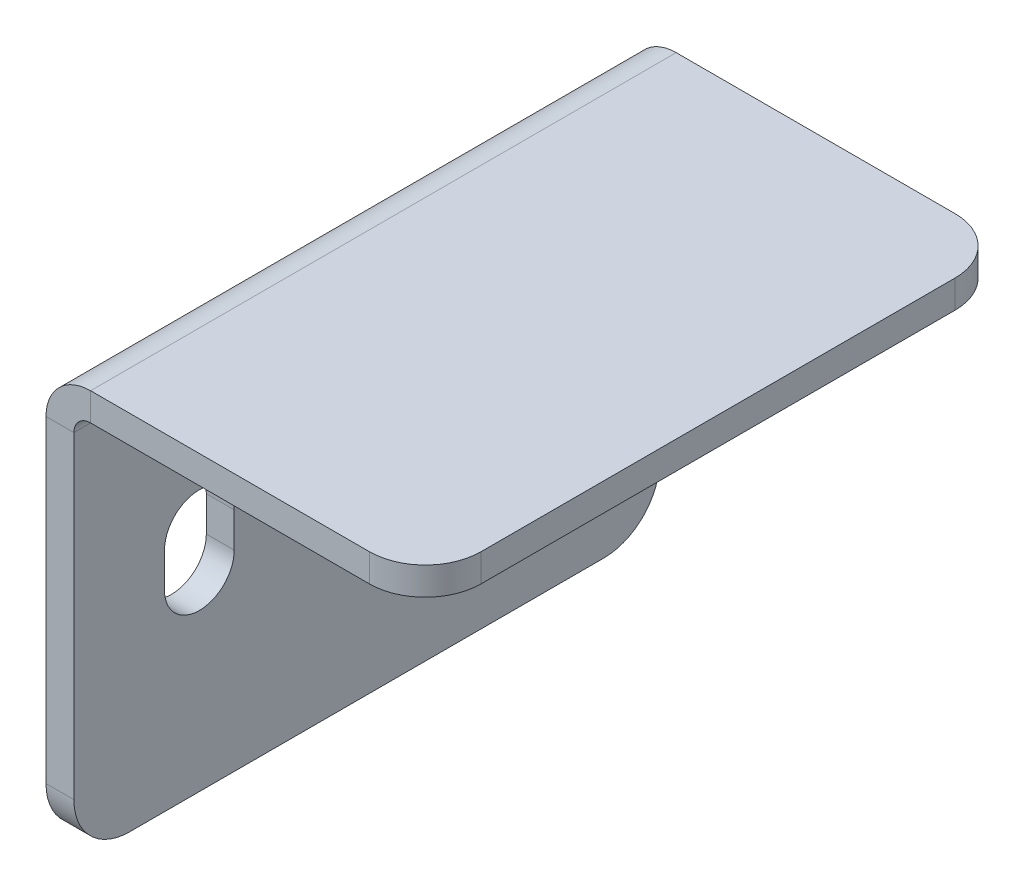
SolidWorks part; units mm, degrees
note: The reader was unsure of these and kept them because the rebuilt part matched: flange length of "Edge-Flange1".
ref_plane "Front Plane" through (0, 0, 0) normal (0, 0, 1) x (1, 0, 0)
ref_plane "Top Plane" through (0, 0, 0) normal (0, 1, 0) x (1, 0, 0)
ref_plane "Right Plane" through (0, 0, 0) normal (1, 0, 0) x (0, 0, -1)
sketch "Sketch1" plane through (0, 0, 0) normal (0, 1, 0) x (1, 0, 0)
  line L1 (-12, 21) -> (12, 21)
  line L2 (-12, 21) -> (-12, -21)
  line L3 (-12, -21) -> (12, -21)
  line L4 (12, 21) -> (12, -21)
  line L5 (-12, 21) -> (12, -21) construction
  line L6 (-12, -21) -> (12, 21) construction
  point P0 (0, 0)
  dimension "D1" = 24
  dimension "D2" = 42
base flange "Base-Flange1" sketch "Sketch1" thickness 2 reverse thickness direction yes parameters "D1"=0.7366
edge flange "Edge-Flange1" sketch "Sketch10" flange angle 90 flange length 30 flange position bend outside bend radius 1.2 thickness 2 relief rectangular parameters "D6"=10
sketch "Sketch10" plane through (-12, 0, 0) normal (1, 0, 0) x (0, 0, 1)
  line L2 (-21, 0) -> (-21, 28)
  line L3 (-21, 28) -> (21, 28)
  line L4 (21, 28) -> (21, 0)
  line L5 (21, 0) -> (-21, 0) construction
  line L6 (21, 0) -> (-21, 0)
bend "EdgeBend1" bend radius 1.2 bend angle 90 parameters "D5"=1
fillet "Fillet1" radius 4 4 edges at (-14.2, -28, -21) (-14.2, -28, 21) (12, 1, -21) (12, 1, 21)
sketch "Sketch11" plane through (-13.2, 0, 0) normal (1, 0, 0) x (0, 0, -1)
  line L0 (9.5, -14.25) -> (9.5, -11.75)
  line L1 (-9.5, -14.25) -> (-9.5, -11.75)
  line L4 (0, -1.2) -> (0, -28) construction
  line L5 (-21, -1.2) -> (21, -1.2) construction
  line L6 (-17, -28) -> (17, -28) construction
  line L7 (-14.5, -14.25) -> (-14.5, -11.75)
  line L8 (14.5, -14.25) -> (14.5, -11.75)
  line L9 (-21, -13) -> (21, -13) construction
  line L10 (-21, -1.2) -> (-21, -24) construction
  line L11 (21, -24) -> (21, -1.2) construction
  arc A0 (-9.5, -11.75) -> (-14.5, -11.75) centre (-12, -11.75) ccw
  arc A2 (-14.5, -14.25) -> (-9.5, -14.25) centre (-12, -14.25) ccw
  arc A3 (14.5, -14.25) -> (9.5, -14.25) centre (12, -14.25) cw
  arc A4 (9.5, -11.75) -> (14.5, -11.75) centre (12, -11.75) cw
  point P3 (-9.5, -13)
  dimension "D1" = 5
  dimension "D2" = 15
  dimension "D3" = 26.8
  dimension "D4" = 15
  dimension "D5" = 9
extrude "Cut-Extrude1" cut sketch "Sketch11" against normal blind 2 normal cut yes
sketch "Bend-Lines1" [suppressed] plane through (0, 0, 0) normal (0, 1, 0) x (1, 0, 0)
sketch "Bounding-Box1" [suppressed] plane through (0, 0, 0) normal (0, 1, 0) x (1, 0, 0)
sheet metal parameters "Sheet-Metal1" thickness 2 parameters "D1"=0.7366
flat pattern "Flat-Pattern1" [suppressed]
sketch "Bend-Lines2" plane through (0, 0, 0) normal (0, 1, 0) x (1, 0, 0)
sketch3d "Bounding-Box2" [suppressed]
  line L0 (12, 21, 0) -> (12, -21, 0) construction
  line L1 (-12, 21, 0) -> (-12, -21, 0) construction
  line L2 (12, 21, 0) -> (-12, 21, 0) construction
  line L3 (12, -21, 0) -> (-12, -21, 0) construction
sheet metal parameters "Sheet-Metal2" thickness 2 parameters "D1"=0.7366
flat pattern "Flat-Pattern1" [suppressed]
sketch "Bend-Lines2" plane through (0, 0, 0) normal (0, -1, 0) x (-1, 0, 0)
  line L0 (13.7279, -21) -> (13.7279, 21) construction
  line L1 (13.7279, -21) -> (13.7279, 21) construction
sketch3d "Bounding-Box2" [suppressed]
  line L0 (42.2558, -21, 0) -> (-12, -21, 0) construction
  line L1 (42.2557, 21, 0) -> (-12, 21, 0) construction
  line L2 (42.2558, -21, 0) -> (42.2557, 21, 0) construction
  line L3 (-12, -21, 0) -> (-12, 21, 0) construction
bend of the flat pattern "Flatten-<EdgeBend1>1"
sketch "Sketch11-1" [suppressed] plane through (-14.2558, 0, 0) normal (0, -1, 0) x (0, 0, -1)
  line L1 (-21, -12.6) -> (21, -12.6) construction
  line L4 (0, -1.2) -> (0, -28) construction
sheet metal parameters "Sheet-Metal3" thickness 2 parameters "D1"=0.7366
flat pattern "Flat-Pattern1" [suppressed]
sketch "Bend-Lines2" plane through (0, 0, 0) normal (0, -1, 0) x (-1, 0, 0)
  line L0 (13.7279, -21) -> (13.7279, 21) construction
  line L1 (13.7279, -21) -> (13.7279, 21) construction
sketch3d "Bounding-Box2" [suppressed]
  line L0 (42.2558, -21, 0) -> (-12, -21, 0) construction
  line L1 (42.2557, 21, 0) -> (-12, 21, 0) construction
  line L2 (42.2558, -21, 0) -> (42.2557, 21, 0) construction
  line L3 (-12, -21, 0) -> (-12, 21, 0) construction
bend of the flat pattern "Flatten-<EdgeBend1>1"
sketch "Sketch11-1" plane through (-14.2558, 0, 0) normal (0, -1, 0) x (0, 0, -1)
  line L0 (9.5, -14.25) -> (9.5, -11.75)
  line L1 (-9.5, -14.25) -> (-9.5, -11.75)
  line L4 (0, -1.2) -> (0, -28) construction
  line L7 (-14.5, -14.25) -> (-14.5, -11.75)
  line L8 (14.5, -14.25) -> (14.5, -11.75)
  line L9 (-21, -13) -> (21, -13) construction
  line L10 (-21, 22.2558) -> (-21, -24) construction
  arc A0 (-9.5, -11.75) -> (-14.5, -11.75) centre (-12, -11.75) ccw
  arc A2 (-14.5, -14.25) -> (-9.5, -14.25) centre (-12, -14.25) ccw
  arc A3 (14.5, -14.25) -> (9.5, -14.25) centre (12, -14.25) cw
  arc A4 (9.5, -11.75) -> (14.5, -11.75) centre (12, -11.75) cw
  dimension "D1" = 5
  dimension "D3" = 26.8
  dimension "D4" = 15
  dimension "D5" = 9
